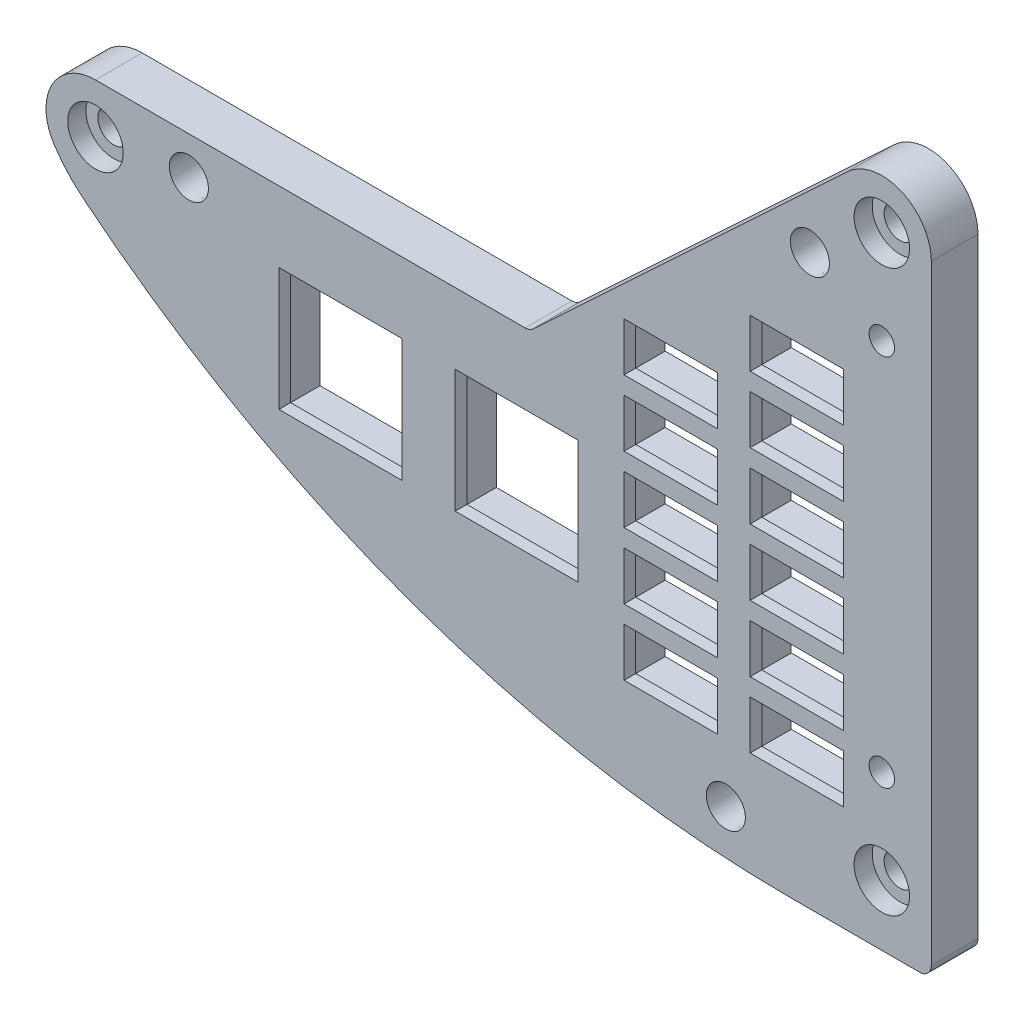
SolidWorks part; units mm, degrees
ref_plane "Front Plane" through (0, 0, 0) normal (0, 0, 1) x (1, 0, 0)
ref_plane "Top Plane" through (0, 0, 0) normal (0, 1, 0) x (1, 0, 0)
ref_plane "Right Plane" through (0, 0, 0) normal (1, 0, 0) x (0, 0, -1)
sketch "Sketch2" plane through (0, 0, -77.851) normal (0, 0, 1) x (1, 0, 0)
  line L0 (-595.8647, 521.6144) -> (-595.8647, 503.8344) construction
  line L1 (-595.8647, 503.8344) -> (-578.0847, 503.8344) construction
  line L2 (-578.0847, 503.8344) -> (-578.0847, 521.6144) construction
  line L3 (-578.0847, 521.6144) -> (-595.8647, 521.6144) construction
  line L4 (-530.5867, 481.6475) -> (-530.5867, 566.1727)
  line L5 (-541.9099, 571.0939) -> (-585.1967, 530.7013)
  line L6 (-585.1967, 530.7013) -> (-644.2517, 530.7013)
  line L7 (-549.6367, 481.6475) -> (-530.5867, 481.6475)
  line L8 (-530.5867, 481.6475) -> (-530.5867, 566.1727)
  line L9 (-541.9099, 571.0939) -> (-585.1967, 530.7013)
  line L10 (-585.1967, 530.7013) -> (-644.2517, 530.7013)
  line L11 (-549.6367, 481.6475) -> (-530.5867, 481.6475)
  line L12 (-572.3697, 495.935) -> (-559.6697, 495.935) construction
  line L13 (-559.6697, 495.935) -> (-559.6697, 502.539) construction
  line L14 (-559.6697, 502.539) -> (-572.3697, 502.539) construction
  line L15 (-572.3697, 502.539) -> (-572.3697, 495.935) construction
  line L16 (-572.3697, 504.9266) -> (-559.6697, 504.9266) construction
  line L17 (-559.6697, 504.9266) -> (-559.6697, 511.5306) construction
  line L18 (-559.6697, 511.5306) -> (-572.3697, 511.5306) construction
  line L19 (-572.3697, 511.5306) -> (-572.3697, 504.9266) construction
  line L20 (-555.2247, 502.539) -> (-555.2247, 495.935) construction
  line L21 (-555.2247, 495.935) -> (-542.5247, 495.935) construction
  line L22 (-542.5247, 495.935) -> (-542.5247, 502.539) construction
  line L23 (-542.5247, 502.539) -> (-555.2247, 502.539) construction
  line L24 (-555.2247, 504.9266) -> (-542.5247, 504.9266) construction
  line L25 (-542.5247, 504.9266) -> (-542.5247, 511.5306) construction
  line L26 (-542.5247, 511.5306) -> (-555.2247, 511.5306) construction
  line L27 (-555.2247, 511.5306) -> (-555.2247, 504.9266) construction
  line L28 (-555.2247, 513.9182) -> (-542.5247, 513.9182) construction
  line L29 (-542.5247, 513.9182) -> (-542.5247, 520.5222) construction
  line L30 (-542.5247, 520.5222) -> (-555.2247, 520.5222) construction
  line L31 (-555.2247, 520.5222) -> (-555.2247, 513.9182) construction
  line L32 (-572.3697, 513.9182) -> (-559.6697, 513.9182) construction
  line L33 (-559.6697, 513.9182) -> (-559.6697, 520.5222) construction
  line L34 (-559.6697, 520.5222) -> (-572.3697, 520.5222) construction
  line L35 (-572.3697, 520.5222) -> (-572.3697, 513.9182) construction
  line L36 (-572.3697, 522.9098) -> (-559.6697, 522.9098) construction
  line L37 (-559.6697, 522.9098) -> (-559.6697, 529.5138) construction
  line L38 (-559.6697, 529.5138) -> (-572.3697, 529.5138) construction
  line L39 (-572.3697, 529.5138) -> (-572.3697, 522.9098) construction
  line L40 (-555.2247, 522.9098) -> (-542.5247, 522.9098) construction
  line L41 (-542.5247, 522.9098) -> (-542.5247, 529.5138) construction
  line L42 (-542.5247, 529.5138) -> (-555.2247, 529.5138) construction
  line L43 (-555.2247, 529.5138) -> (-555.2247, 522.9098) construction
  line L44 (-555.2247, 531.9014) -> (-542.5247, 531.9014) construction
  line L45 (-542.5247, 531.9014) -> (-542.5247, 538.5054) construction
  line L46 (-542.5247, 538.5054) -> (-555.2247, 538.5054) construction
  line L47 (-555.2247, 538.5054) -> (-555.2247, 531.9014) construction
  line L48 (-572.3697, 531.9014) -> (-559.6697, 531.9014) construction
  line L49 (-559.6697, 531.9014) -> (-559.6697, 538.5054) construction
  line L50 (-559.6697, 538.5054) -> (-572.3697, 538.5054) construction
  line L51 (-572.3697, 538.5054) -> (-572.3697, 531.9014) construction
  line L52 (-555.2247, 540.893) -> (-542.5247, 540.893) construction
  line L53 (-542.5247, 540.893) -> (-542.5247, 547.497) construction
  line L54 (-542.5247, 547.497) -> (-555.2247, 547.497) construction
  line L55 (-555.2247, 547.497) -> (-555.2247, 540.893) construction
  line L56 (-555.2247, 513.9182) -> (-542.5247, 513.9182) construction
  line L57 (-595.8647, 521.6144) -> (-595.8647, 503.8344) construction
  line L58 (-595.8647, 503.8344) -> (-578.0847, 503.8344) construction
  line L59 (-578.0847, 503.8344) -> (-578.0847, 521.6144) construction
  line L60 (-578.0847, 521.6144) -> (-595.8647, 521.6144) construction
  line L61 (-572.3697, 495.935) -> (-559.6697, 495.935)
  line L62 (-559.6697, 495.935) -> (-559.6697, 502.539)
  line L63 (-559.6697, 502.539) -> (-572.3697, 502.539)
  line L64 (-572.3697, 502.539) -> (-572.3697, 495.935)
  line L65 (-572.3697, 504.9266) -> (-559.6697, 504.9266)
  line L66 (-559.6697, 504.9266) -> (-559.6697, 511.5306)
  line L67 (-559.6697, 511.5306) -> (-572.3697, 511.5306)
  line L68 (-572.3697, 511.5306) -> (-572.3697, 504.9266)
  line L69 (-555.2247, 502.539) -> (-555.2247, 495.935)
  line L70 (-555.2247, 495.935) -> (-542.5247, 495.935)
  line L71 (-542.5247, 495.935) -> (-542.5247, 502.539)
  line L72 (-542.5247, 502.539) -> (-555.2247, 502.539)
  line L73 (-555.2247, 504.9266) -> (-542.5247, 504.9266)
  line L74 (-542.5247, 504.9266) -> (-542.5247, 511.5306)
  line L75 (-542.5247, 511.5306) -> (-555.2247, 511.5306)
  line L76 (-555.2247, 511.5306) -> (-555.2247, 504.9266)
  line L77 (-555.2247, 513.9182) -> (-542.5247, 513.9182)
  line L78 (-542.5247, 513.9182) -> (-542.5247, 520.5222)
  line L79 (-542.5247, 520.5222) -> (-555.2247, 520.5222)
  line L80 (-555.2247, 520.5222) -> (-555.2247, 513.9182)
  line L81 (-572.3697, 513.9182) -> (-559.6697, 513.9182)
  line L82 (-559.6697, 513.9182) -> (-559.6697, 520.5222)
  line L83 (-559.6697, 520.5222) -> (-572.3697, 520.5222)
  line L84 (-572.3697, 520.5222) -> (-572.3697, 513.9182)
  line L85 (-572.3697, 522.9098) -> (-559.6697, 522.9098)
  line L86 (-559.6697, 522.9098) -> (-559.6697, 529.5138)
  line L87 (-559.6697, 529.5138) -> (-572.3697, 529.5138)
  line L88 (-572.3697, 529.5138) -> (-572.3697, 522.9098)
  line L89 (-555.2247, 522.9098) -> (-542.5247, 522.9098)
  line L90 (-542.5247, 522.9098) -> (-542.5247, 529.5138)
  line L91 (-542.5247, 529.5138) -> (-555.2247, 529.5138)
  line L92 (-555.2247, 529.5138) -> (-555.2247, 522.9098)
  line L93 (-555.2247, 531.9014) -> (-542.5247, 531.9014)
  line L94 (-542.5247, 531.9014) -> (-542.5247, 538.5054)
  line L95 (-542.5247, 538.5054) -> (-555.2247, 538.5054)
  line L96 (-555.2247, 538.5054) -> (-555.2247, 531.9014)
  line L97 (-572.3697, 531.9014) -> (-559.6697, 531.9014)
  line L98 (-559.6697, 531.9014) -> (-559.6697, 538.5054)
  line L99 (-559.6697, 538.5054) -> (-572.3697, 538.5054)
  line L100 (-572.3697, 538.5054) -> (-572.3697, 531.9014)
  line L101 (-555.2247, 540.893) -> (-542.5247, 540.893)
  line L102 (-542.5247, 540.893) -> (-542.5247, 547.497)
  line L103 (-542.5247, 547.497) -> (-555.2247, 547.497)
  line L104 (-555.2247, 547.497) -> (-555.2247, 540.893)
  line L105 (-555.2247, 513.9182) -> (-542.5247, 513.9182)
  line L106 (-578.0847, 503.8344) -> (-595.8647, 521.6144) construction
  line L108 (-578.6181, 521.081) -> (-595.3313, 521.081)
  line L109 (-578.6181, 521.081) -> (-578.6181, 504.3678)
  line L110 (-578.6181, 504.3678) -> (-595.3313, 504.3678)
  line L111 (-595.3313, 521.081) -> (-595.3313, 504.3678)
  line L112 (-578.6181, 521.081) -> (-595.3313, 504.3678) construction
  line L113 (-578.6181, 504.3678) -> (-595.3313, 521.081) construction
  arc A4 (-530.5867, 566.1727) -> (-541.9099, 571.0939) centre (-537.3177, 566.1727) ccw
  arc A5 (-644.2517, 530.7013) -> (-649.8762, 520.2727) centre (-644.2517, 523.9703) ccw
  arc A6 (-649.8762, 520.2727) -> (-646.0191, 515.9958) centre (-634.0129, 530.7013) ccw
  arc A7 (-646.0191, 515.9958) -> (-549.6367, 481.6475) centre (-549.6367, 634.0475) ccw
  arc A8 (-530.5867, 566.1727) -> (-541.9099, 571.0939) centre (-537.3177, 566.1727) ccw
  arc A9 (-644.2517, 530.7013) -> (-649.8762, 520.2727) centre (-644.2517, 523.9703) ccw
  arc A10 (-649.8762, 520.2727) -> (-646.0191, 515.9958) centre (-634.0129, 530.7013) ccw
  arc A11 (-646.0191, 515.9958) -> (-549.6367, 481.6475) centre (-549.6367, 634.0475) ccw
  point P58 (-586.9747, 512.7244)
  dimension "D2" = 16.7132
  dimension "D1" = 0
extrude "Boss-Extrude1" add sketch "Sketch2" against normal blind 6.35 contours A10 A11 L11 L8 A8 L9 L10 A9 L60 L59 L58 L57 L64 L63 L62 L61 L68 L67 L66 L65 L72 L71 L70 L69 L76 L75 L74 L73 L80 L79 L78 L77 L84 L83 L82 L81 L88 L87 L86 L85 L92 L91 region at (-576.7506, 517.828, -77.851)
hole_wizard "CBORE for #6 Pan Head Machine Screw1" positions "Sketch4" profile "Sketch3" counterbore size "#6" standard "ANSI Inch" end condition through all
sketch "Sketch4" plane through (0, 0, -77.851) normal (0, 0, 1) x (1, 0, 0)
  point P0 (-537.3177, 489.9025)
  point P3 (-537.3177, 566.1727)
  point P6 (-644.2517, 523.9703)
sketch "Sketch3" plane through (-537.3177, 489.9025, -77.851) normal (1, 0, 0) x (0, -1, 0)
  line L0 (0, 0) -> (0, 6.35)
  line L1 (0, 6.35) -> (2.1526, 6.35)
  line L3 (2.1526, 6.35) -> (2.1526, 2.4638)
  line L4 (2.1526, 2.4638) -> (3.7706, 2.4638)
  line L5 (3.7706, 2.4638) -> (3.7706, 0)
  line L7 (3.7706, 0) -> (0, 0)
  line L11 (0, -6.35) -> (0, 107.95) construction
  dimension "Thru Hole Dia." = 4.3053
  dimension "Thru Hole Depth" = 6.35
  dimension "C'Bore Dia." = 7.5413
  dimension "C'Bore Depth" = 2.4638
hole_wizard "#6 Threaded Insert Tapered Hole" positions "Sketch6" profile "Sketch5" legacy
sketch "Sketch6" plane through (0, 0, -77.851) normal (0, 0, 1) x (1, 0, 0)
  point P0 (-558.5267, 487.9975)
  point P3 (-547.0967, 558.9583)
  point P6 (-631.5517, 525.5578)
sketch "Sketch5" plane through (-558.5267, 487.9975, -77.851) normal (1, 0, 0) x (0, -1, 0)
  line L0 (0, 0) -> (0, 3.81)
  line L1 (0, 3.81) -> (2.5273, 3.81)
  line L2 (2.5273, 3.81) -> (2.6543, 0)
  line L3 (2.6543, 0) -> (0, 0)
  line L4 (0, 110) -> (0, -10) construction
  dimension "Minor Diameter" = 5.0546
  dimension "Depth" = 3.81
  dimension "Major Diameter" = 5.3086
sketch "Sketch7" plane through (0, 0, -77.851) normal (0, 0, 1) x (1, 0, 0)
  line L0 (-610.9485, 512.7244) -> (-610.9485, 521.081) construction
  line L2 (-610.9485, 512.7244) -> (-595.3313, 512.7244) construction
  line L3 (-602.5919, 504.3678) -> (-619.3051, 504.3678)
  line L4 (-602.5919, 504.3678) -> (-602.5919, 521.081)
  line L5 (-602.5919, 521.081) -> (-619.3051, 521.081)
  line L6 (-619.3051, 504.3678) -> (-619.3051, 521.081)
  line L7 (-602.5919, 504.3678) -> (-619.3051, 521.081) construction
  line L8 (-602.5919, 521.081) -> (-619.3051, 504.3678) construction
  line L9 (-595.3313, 521.081) -> (-595.3313, 504.3678) construction
  point P5 (-610.9485, 512.7244)
  dimension "D1" = 16.7132
  dimension "D2" = 16.7132
  dimension "D3" = 15.6171
extrude "Cut-Extrude1" cut sketch "Sketch7" against normal through all
sketch "Sketch8" plane through (0, 0, -84.201) normal (0, 0, -1) x (-1, 0, 0)
  line L0 (555.9867, 540.131) -> (555.9867, 548.259)
  line L1 (555.9867, 548.259) -> (541.7627, 548.259)
  line L2 (541.7627, 548.259) -> (541.7627, 540.131)
  line L3 (541.7627, 540.131) -> (555.9867, 540.131)
  line L4 (555.2247, 540.893) -> (555.2247, 547.497)
  line L5 (542.5247, 540.893) -> (555.2247, 540.893)
  line L6 (542.5247, 547.497) -> (542.5247, 540.893)
  line L7 (555.2247, 547.497) -> (542.5247, 547.497)
  line L8 (555.2247, 540.893) -> (555.2247, 547.497) construction
  line L9 (542.5247, 540.893) -> (555.2247, 540.893) construction
  line L10 (542.5247, 547.497) -> (542.5247, 540.893) construction
  line L11 (555.2247, 547.497) -> (542.5247, 547.497) construction
  line L12 (555.2247, 531.9014) -> (555.2247, 538.5054)
  line L13 (542.5247, 531.9014) -> (555.2247, 531.9014)
  line L14 (542.5247, 538.5054) -> (542.5247, 531.9014)
  line L15 (555.2247, 538.5054) -> (542.5247, 538.5054)
  line L16 (555.2247, 531.9014) -> (555.2247, 538.5054) construction
  line L17 (542.5247, 531.9014) -> (555.2247, 531.9014) construction
  line L18 (542.5247, 538.5054) -> (542.5247, 531.9014) construction
  line L19 (555.2247, 538.5054) -> (542.5247, 538.5054) construction
  line L20 (555.2247, 522.9098) -> (555.2247, 529.5138)
  line L21 (542.5247, 522.9098) -> (555.2247, 522.9098)
  line L22 (542.5247, 529.5138) -> (542.5247, 522.9098)
  line L23 (555.2247, 529.5138) -> (542.5247, 529.5138)
  line L24 (555.2247, 522.9098) -> (555.2247, 529.5138) construction
  line L25 (542.5247, 522.9098) -> (555.2247, 522.9098) construction
  line L26 (542.5247, 529.5138) -> (542.5247, 522.9098) construction
  line L27 (555.2247, 529.5138) -> (542.5247, 529.5138) construction
  line L28 (555.2247, 513.9182) -> (555.2247, 520.5222)
  line L29 (542.5247, 513.9182) -> (555.2247, 513.9182)
  line L30 (542.5247, 520.5222) -> (542.5247, 513.9182)
  line L31 (555.2247, 520.5222) -> (542.5247, 520.5222)
  line L32 (555.2247, 513.9182) -> (555.2247, 520.5222) construction
  line L33 (542.5247, 513.9182) -> (555.2247, 513.9182) construction
  line L34 (542.5247, 520.5222) -> (542.5247, 513.9182) construction
  line L35 (555.2247, 520.5222) -> (542.5247, 520.5222) construction
  line L36 (555.2247, 504.9266) -> (555.2247, 511.5306)
  line L37 (542.5247, 504.9266) -> (555.2247, 504.9266)
  line L38 (542.5247, 511.5306) -> (542.5247, 504.9266)
  line L39 (555.2247, 511.5306) -> (542.5247, 511.5306)
  line L40 (555.2247, 504.9266) -> (555.2247, 511.5306) construction
  line L41 (542.5247, 504.9266) -> (555.2247, 504.9266) construction
  line L42 (542.5247, 511.5306) -> (542.5247, 504.9266) construction
  line L43 (555.2247, 511.5306) -> (542.5247, 511.5306) construction
  line L44 (555.2247, 502.539) -> (542.5247, 502.539)
  line L45 (555.2247, 495.935) -> (555.2247, 502.539)
  line L46 (542.5247, 495.935) -> (555.2247, 495.935)
  line L47 (542.5247, 502.539) -> (542.5247, 495.935)
  line L48 (555.2247, 502.539) -> (542.5247, 502.539) construction
  line L49 (555.2247, 495.935) -> (555.2247, 502.539) construction
  line L50 (542.5247, 495.935) -> (555.2247, 495.935) construction
  line L51 (542.5247, 502.539) -> (542.5247, 495.935) construction
  line L52 (572.3697, 531.9014) -> (572.3697, 538.5054)
  line L53 (559.6697, 531.9014) -> (572.3697, 531.9014)
  line L54 (559.6697, 538.5054) -> (559.6697, 531.9014)
  line L55 (572.3697, 538.5054) -> (559.6697, 538.5054)
  line L56 (572.3697, 531.9014) -> (572.3697, 538.5054) construction
  line L57 (559.6697, 531.9014) -> (572.3697, 531.9014) construction
  line L58 (559.6697, 538.5054) -> (559.6697, 531.9014) construction
  line L59 (572.3697, 538.5054) -> (559.6697, 538.5054) construction
  line L60 (572.3697, 522.9098) -> (572.3697, 529.5138)
  line L61 (559.6697, 522.9098) -> (572.3697, 522.9098)
  line L62 (559.6697, 529.5138) -> (559.6697, 522.9098)
  line L63 (572.3697, 529.5138) -> (559.6697, 529.5138)
  line L64 (572.3697, 522.9098) -> (572.3697, 529.5138) construction
  line L65 (559.6697, 522.9098) -> (572.3697, 522.9098) construction
  line L66 (559.6697, 529.5138) -> (559.6697, 522.9098) construction
  line L67 (572.3697, 529.5138) -> (559.6697, 529.5138) construction
  line L68 (572.3697, 513.9182) -> (572.3697, 520.5222)
  line L69 (559.6697, 513.9182) -> (572.3697, 513.9182)
  line L70 (559.6697, 520.5222) -> (559.6697, 513.9182)
  line L71 (572.3697, 520.5222) -> (559.6697, 520.5222)
  line L72 (572.3697, 513.9182) -> (572.3697, 520.5222) construction
  line L73 (559.6697, 513.9182) -> (572.3697, 513.9182) construction
  line L74 (559.6697, 520.5222) -> (559.6697, 513.9182) construction
  line L75 (572.3697, 520.5222) -> (559.6697, 520.5222) construction
  line L76 (572.3697, 504.9266) -> (572.3697, 511.5306)
  line L77 (559.6697, 504.9266) -> (572.3697, 504.9266)
  line L78 (559.6697, 511.5306) -> (559.6697, 504.9266)
  line L79 (572.3697, 511.5306) -> (559.6697, 511.5306)
  line L80 (572.3697, 504.9266) -> (572.3697, 511.5306) construction
  line L81 (559.6697, 504.9266) -> (572.3697, 504.9266) construction
  line L82 (559.6697, 511.5306) -> (559.6697, 504.9266) construction
  line L83 (572.3697, 511.5306) -> (559.6697, 511.5306) construction
  line L84 (572.3697, 495.935) -> (572.3697, 502.539)
  line L85 (559.6697, 495.935) -> (572.3697, 495.935)
  line L86 (559.6697, 502.539) -> (559.6697, 495.935)
  line L87 (572.3697, 502.539) -> (559.6697, 502.539)
  line L88 (572.3697, 495.935) -> (572.3697, 502.539) construction
  line L89 (559.6697, 495.935) -> (572.3697, 495.935) construction
  line L90 (559.6697, 502.539) -> (559.6697, 495.935) construction
  line L91 (572.3697, 502.539) -> (559.6697, 502.539) construction
  line L92 (595.3313, 504.3678) -> (595.3313, 521.081)
  line L93 (578.6181, 504.3678) -> (595.3313, 504.3678)
  line L94 (578.6181, 521.081) -> (578.6181, 504.3678)
  line L95 (595.3313, 521.081) -> (578.6181, 521.081)
  line L96 (595.3313, 504.3678) -> (595.3313, 521.081) construction
  line L97 (578.6181, 504.3678) -> (595.3313, 504.3678) construction
  line L98 (578.6181, 521.081) -> (578.6181, 504.3678) construction
  line L99 (595.3313, 521.081) -> (578.6181, 521.081) construction
  line L100 (555.9867, 531.1394) -> (555.9867, 539.2674)
  line L101 (555.9867, 539.2674) -> (541.7627, 539.2674)
  line L102 (541.7627, 539.2674) -> (541.7627, 531.1394)
  line L103 (541.7627, 531.1394) -> (555.9867, 531.1394)
  line L104 (555.9867, 522.1478) -> (555.9867, 530.2758)
  line L105 (555.9867, 530.2758) -> (541.7627, 530.2758)
  line L106 (541.7627, 530.2758) -> (541.7627, 522.1478)
  line L107 (541.7627, 522.1478) -> (555.9867, 522.1478)
  line L108 (555.9867, 513.1562) -> (555.9867, 521.2842)
  line L109 (555.9867, 521.2842) -> (541.7627, 521.2842)
  line L110 (541.7627, 521.2842) -> (541.7627, 513.1562)
  line L111 (541.7627, 513.1562) -> (555.9867, 513.1562)
  line L112 (555.9867, 504.1646) -> (555.9867, 512.2926)
  line L113 (555.9867, 512.2926) -> (541.7627, 512.2926)
  line L114 (541.7627, 512.2926) -> (541.7627, 504.1646)
  line L115 (541.7627, 504.1646) -> (555.9867, 504.1646)
  line L116 (555.9867, 503.301) -> (541.7627, 503.301)
  line L117 (541.7627, 503.301) -> (541.7627, 495.173)
  line L118 (541.7627, 495.173) -> (555.9867, 495.173)
  line L119 (555.9867, 495.173) -> (555.9867, 503.301)
  line L120 (573.1317, 531.1394) -> (573.1317, 539.2674)
  line L121 (573.1317, 539.2674) -> (558.9077, 539.2674)
  line L122 (558.9077, 539.2674) -> (558.9077, 531.1394)
  line L123 (558.9077, 531.1394) -> (573.1317, 531.1394)
  line L124 (573.1317, 522.1478) -> (573.1317, 530.2758)
  line L125 (573.1317, 530.2758) -> (558.9077, 530.2758)
  line L126 (558.9077, 530.2758) -> (558.9077, 522.1478)
  line L127 (558.9077, 522.1478) -> (573.1317, 522.1478)
  line L128 (573.1317, 513.1562) -> (573.1317, 521.2842)
  line L129 (573.1317, 521.2842) -> (558.9077, 521.2842)
  line L130 (558.9077, 521.2842) -> (558.9077, 513.1562)
  line L131 (558.9077, 513.1562) -> (573.1317, 513.1562)
  line L132 (573.1317, 504.1646) -> (573.1317, 512.2926)
  line L133 (573.1317, 512.2926) -> (558.9077, 512.2926)
  line L134 (558.9077, 512.2926) -> (558.9077, 504.1646)
  line L135 (558.9077, 504.1646) -> (573.1317, 504.1646)
  line L136 (573.1317, 495.173) -> (573.1317, 503.301)
  line L137 (573.1317, 503.301) -> (558.9077, 503.301)
  line L138 (558.9077, 503.301) -> (558.9077, 495.173)
  line L139 (558.9077, 495.173) -> (573.1317, 495.173)
  line L140 (596.0933, 503.6058) -> (596.0933, 521.843)
  line L141 (596.0933, 521.843) -> (577.8561, 521.843)
  line L142 (577.8561, 521.843) -> (577.8561, 503.6058)
  line L143 (577.8561, 503.6058) -> (596.0933, 503.6058)
  line L144 (620.0671, 521.843) -> (601.8299, 521.843)
  line L145 (601.8299, 521.843) -> (601.8299, 503.6058)
  line L146 (601.8299, 503.6058) -> (620.0671, 503.6058)
  line L147 (620.0671, 503.6058) -> (620.0671, 521.843)
  line L148 (619.3051, 521.081) -> (602.5919, 521.081)
  line L149 (619.3051, 504.3678) -> (619.3051, 521.081)
  line L150 (602.5919, 504.3678) -> (619.3051, 504.3678)
  line L151 (602.5919, 521.081) -> (602.5919, 504.3678)
  line L152 (619.3051, 521.081) -> (602.5919, 521.081) construction
  line L153 (619.3051, 504.3678) -> (619.3051, 521.081) construction
  line L154 (602.5919, 504.3678) -> (619.3051, 504.3678) construction
  line L155 (602.5919, 521.081) -> (602.5919, 504.3678) construction
  dimension "D1" = 0
  dimension "D2" = 0
  dimension "D3" = 0
  dimension "D4" = 0
  dimension "D5" = 0
  dimension "D6" = 0
  dimension "D7" = 0
  dimension "D8" = 0
  dimension "D9" = 0
  dimension "D10" = 0
  dimension "D11" = 0
  dimension "D12" = 0
  dimension "D13" = 0.762
  dimension "D14" = 0
  dimension "D15" = 0.762
extrude "Cut-Extrude2" cut sketch "Sketch8" against normal offset from surface (4.7625 mm away) 1.5875 up to face at (-610.9485, 512.7244, -77.851)
fillet "Fillet1" radius 1.5875 2 edges at (-585.1967, 530.7013, -81.026) (-530.5867, 481.6475, -81.026)
hole_wizard "#4 Clearance Hole1" positions "Sketch10" profile "Sketch9" hole size "#4" standard "ANSI Inch" end condition through all
sketch "Sketch10" plane through (0, 0, -77.851) normal (0, 0, 1) x (1, 0, 0)
  point P0 (-537.3177, 502.6376)
  point P3 (-537.3177, 553.4376)
sketch "Sketch9" plane through (-537.3177, 502.6376, -77.851) normal (1, 0, 0) x (0, -1, 0)
  line L0 (0, 0) -> (0, 6.35)
  line L1 (0, 6.35) -> (1.7272, 6.35)
  line L2 (1.7272, 6.35) -> (1.7272, 0)
  line L5 (1.7272, 0) -> (0, 0)
  line L11 (0, -6.35) -> (0, 107.95) construction
  dimension "Thru Hole Dia." = 3.4544
  dimension "Thru Hole Depth" = 6.35
hole_wizard "Hole2" positions "Sketch12" profile "Sketch11" legacy
sketch "Sketch12" plane through (0, 0, -84.201) normal (0, 0, -1) x (-1, 0, 0)
  point P0 (642.6555, 517.9926)
sketch "Sketch11" plane through (-642.6555, 517.9926, -84.201) normal (1, 0, 0) x (0, 1, 0)
  line L0 (0, 0) -> (0, 3.429)
  line L1 (0, 3.429) -> (1.9431, 3.429)
  line L2 (1.9431, 3.429) -> (2.0701, 0)
  line L3 (2.0701, 0) -> (0, 0)
  line L4 (0, 110) -> (0, -10) construction
  dimension "Minor Diameter" = 3.8862
  dimension "Depth" = 3.429
  dimension "Major Diameter" = 4.1402
hole_wizard "#4 Clearance Hole2" positions "Sketch14" profile "Sketch13" hole size "#4" standard "ANSI Inch"
sketch "Sketch14" plane through (0, 0, -80.772) normal (0, 0, -1) x (-1, 0, 0)
  point P2 (642.6555, 517.9926)
sketch "Sketch13" plane through (-642.6555, 517.9926, -80.772) normal (1, 0, 0) x (0, 1, 0)
  line L0 (0, 0) -> (0, 1.5875)
  line L1 (0, 1.5875) -> (1.7272, 1.5875)
  line L2 (1.7272, 1.5875) -> (1.7272, 0)
  line L5 (1.7272, 0) -> (0, 0)
  line L10 (0, 1.5875) -> (-1.7272, 1.5875) construction
  line L11 (0, -6.35) -> (0, 107.95) construction
  dimension "Hole Dia." = 3.4544
  dimension "Hole Depth" = 1.5875
  dimension "Drill Angle" = 180
hole_wizard "#6 Clearance Hole1" positions "Sketch16" profile "Sketch15" hole size "#6" standard "ANSI Inch" end condition through all
sketch "Sketch16" plane through (0, 0, -81.661) normal (0, 0, 1) x (1, 0, 0)
  point P0 (-558.5267, 487.9975)
  point P3 (-631.5517, 525.5578)
  point P6 (-547.0967, 558.9583)
sketch "Sketch15" plane through (-558.5267, 487.9975, -81.661) normal (1, 0, 0) x (0, -1, 0)
  line L0 (0, 0) -> (0, 2.54)
  line L1 (0, 2.54) -> (2.1526, 2.54)
  line L2 (2.1526, 2.54) -> (2.1526, 0)
  line L5 (2.1526, 0) -> (0, 0)
  line L11 (0, -6.35) -> (0, 107.95) construction
  dimension "Thru Hole Dia." = 4.3053
  dimension "Thru Hole Depth" = 2.54
equation "\"D2@Sketch7\"=\"D1@Sketch7\""
